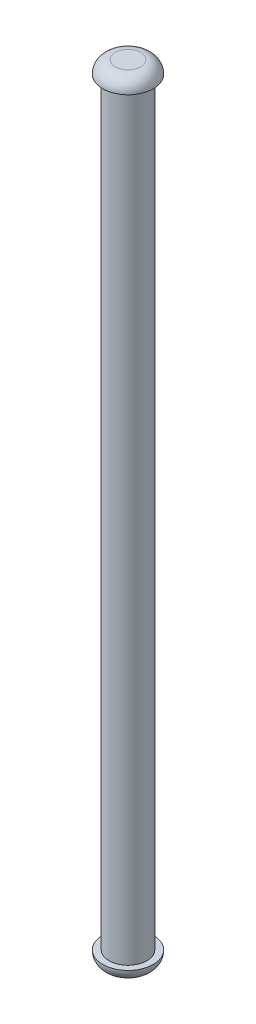
SolidWorks part; units mm, degrees
ref_plane "Front Plane" through (0, 0, 0) normal (0, 0, 1) x (1, 0, 0)
ref_plane "Top Plane" through (0, 0, 0) normal (0, 1, 0) x (1, 0, 0)
ref_plane "Right Plane" through (0, 0, 0) normal (1, 0, 0) x (0, 0, -1)
sketch "Szkic1" plane through (0, 0, 0) normal (0, 1, 0) x (1, 0, 0)
  circle A0 centre (0, 0) radius 1.5
extrude "Dodanie-wyciągnięcie1" add sketch "Szkic1" along normal blind 60
sketch "Szkic2" plane through (0, 60, 0) normal (0, 1, 0) x (1, 0, 0)
  circle A0 centre (0, 0) radius 2
extrude "Dodanie-wyciągnięcie2" add sketch "Szkic2" along normal blind 1
fillet "Zaokrąglenie1" radius 1 1 edges at (0, 61, 2)
sketch "Szkic3" plane through (0, 0, 0) normal (0, -1, 0) x (1, 0, 0)
  circle A0 centre (0, 0) radius 2
extrude "Dodanie-wyciągnięcie3" add sketch "Szkic3" along normal blind 1
fillet "Zaokrąglenie2" radius 1 1 edges at (0, -1, -2)
